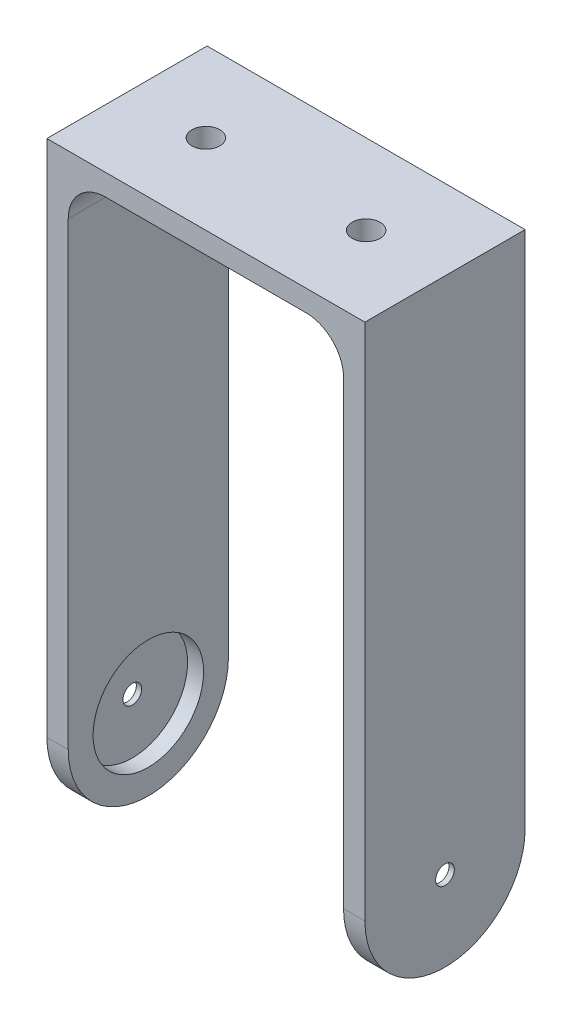
SolidWorks part; units mm, degrees
ref_plane "前视基准面" through (0, 0, 0) normal (0, 0, 1) x (1, 0, 0)
ref_plane "上视基准面" through (0, 0, 0) normal (0, 1, 0) x (1, 0, 0)
ref_plane "右视基准面" through (0, 0, 0) normal (1, 0, 0) x (0, 0, -1)
sketch "草图1" plane through (0, 0, 0) normal (0, 0, 1) x (1, 0, 0)
  line L0 (0, 0) -> (0, 113.274) construction
  line L1 (0, -133.973) -> (0, 133.973) construction
  line L2 (29.774, -24.3) -> (29.774, 97.1173)
  line L4 (29.774, 97.1173) -> (0, 97.1173)
  line L6 (-29.774, 97.1173) -> (0, 97.1173)
  line L7 (-29.774, -24.3) -> (-29.774, 97.1173)
extrude "拉伸-薄壁2" add sketch "草图1" along normal mid plane 30 thin thin type one direction wall 4
sketch "草图2" plane through (0, 97.1173, 0) normal (0, 1, 0) x (1, 0, 0)
  circle A0 centre (-15, 0) radius 2.6207
  circle A1 centre (0, 0) radius 15 construction
  circle A2 centre (15, 0) radius 2.6207
  point P10 (0, 0)
  dimension "D1" = 2
extrude "切除-拉伸1" cut sketch "草图2" against normal blind 30
sketch "草图4" plane through (25.774, 0, 0) normal (-1, 0, 0) x (0, 0, 1)
  line L8 (-2.7763, 22.1639) -> (-5.0902, 4.5089)
  line L9 (-5.0902, -4.5089) -> (-2.7763, -22.1639)
  line L10 (2.7763, -22.1639) -> (5.0902, -4.5089)
  line L11 (5.0902, 4.5089) -> (2.7763, 22.1639)
  line L12 (-2.7763, 22.1639) -> (-5.0902, 4.5089)
  line L13 (-5.0902, -4.5089) -> (-2.7763, -22.1639)
  line L14 (2.7763, -22.1639) -> (5.0902, -4.5089)
  line L15 (5.0902, 4.5089) -> (2.7763, 22.1639)
  arc A8 (2.7763, 22.1639) -> (-2.7763, 22.1639) centre (0, 21.8) ccw
  arc A9 (-5.0902, 4.5089) -> (-5.0902, -4.5089) centre (0, 0) ccw
  arc A10 (-2.7763, -22.1639) -> (2.7763, -22.1639) centre (0, -21.8) ccw
  arc A11 (5.0902, -4.5089) -> (5.0902, 4.5089) centre (0, 0) ccw
  arc A12 (2.7763, 22.1639) -> (-2.7763, 22.1639) centre (0, 21.8) ccw
  arc A13 (-5.0902, 4.5089) -> (-5.0902, -4.5089) centre (0, 0) ccw
  arc A14 (-2.7763, -22.1639) -> (2.7763, -22.1639) centre (0, -21.8) ccw
  arc A15 (5.0902, -4.5089) -> (5.0902, 4.5089) centre (0, 0) ccw
  dimension "D1" = 0.3
extrude "切除-拉伸2" cut sketch "草图4" against normal blind 3
sketch "草图5" plane through (-25.774, 0, 0) normal (1, 0, 0) x (0, 0, -1)
  circle A0 centre (0, 0) radius 10.35
extrude "切除-拉伸3" cut sketch "草图5" against normal blind 3
sketch "草图6" plane through (-29.774, 0, 0) normal (-1, 0, 0) x (0, 0, 1)
  circle A0 centre (0, 0) radius 1.75
extrude "切除-拉伸4" cut sketch "草图6" against normal blind 73
fillet "圆角1" radius 7 2 edges at (25.774, 93.1173, 0) (-25.774, 93.1173, 0)
fillet "圆角2" radius 15 4 edges at (27.774, -24.3, -15) (-27.774, -24.3, -15) (-27.774, -24.3, 15) (27.774, -24.3, 15)
sketch "草图7" plane through (-29.774, 0, 0) normal (-1, 0, 0) x (0, 0, 1)
  line L3 (-15, 97.1173) -> (-15, -9.3)
  line L4 (15, -9.3) -> (15, 97.1173)
  line L5 (15, 97.1173) -> (-15, 97.1173)
  line L6 (-15, 0) -> (-15, -9.3)
  line L7 (15, -9.3) -> (15, 0)
  line L8 (15, 97.1173) -> (-15, 97.1173)
  arc A0 (-15, 0) -> (15, 0) centre (0, 0) ccw
  arc A3 (-15, -9.3) -> (0, -24.3) centre (0, -9.3) ccw
  arc A4 (0, -24.3) -> (15, -9.3) centre (0, -9.3) ccw
  arc A5 (-15, -9.3) -> (0, -24.3) centre (0, -9.3) ccw
  arc A6 (0, -24.3) -> (15, -9.3) centre (0, -9.3) ccw
  line M7 (-15, 97.1173) -> (-15, -9.3)
  arc M8 (-15, -9.3) -> (0, -24.3) centre (0, -9.3) ccw
  arc M9 (0, -24.3) -> (15, -9.3) centre (0, -9.3) ccw
  line M10 (15, -9.3) -> (15, 97.1173)
  dimension "D1" = 0
extrude "切除-拉伸5" cut sketch "草图7" against normal blind 80 contours A0 M7 M8 M9 M10
